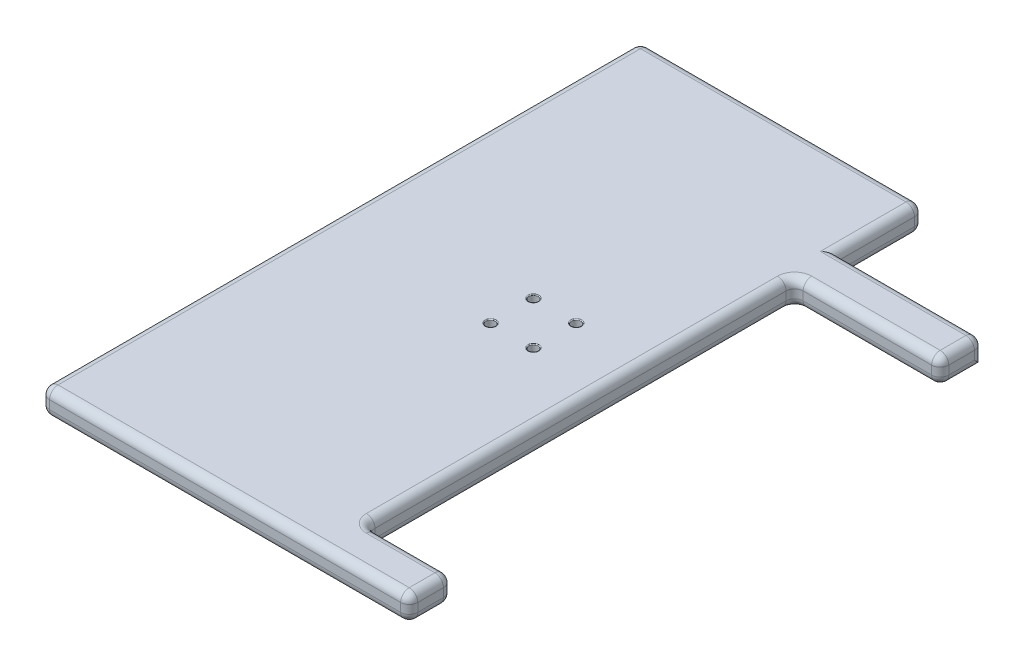
SolidWorks part; units mm, degrees
ref_plane "前视基准面" through (0, 0, 0) normal (0, 0, 1) x (1, 0, 0)
ref_plane "上视基准面" through (0, 0, 0) normal (0, 1, 0) x (1, 0, 0)
ref_plane "右视基准面" through (0, 0, 0) normal (1, 0, 0) x (0, 0, -1)
other "Configuration Table"
sketch "草图1" plane through (0, 0, 0) normal (0, 1, 0) x (1, 0, 0)
  line L0 (26, -60) -> (26, -70)
  line L1 (-60, 70) -> (6, 70)
  line L2 (-60, 70) -> (-60, -70)
  line L3 (-60, -70) -> (26, -70)
  line L4 (40, 50) -> (40, 40)
  line L5 (-55, 0) -> (55, 0) construction
  line L6 (0, -55) -> (0, 55) construction
  line L7 (6, 70) -> (6, 50)
  line L8 (6, 50) -> (40, 50)
  line L10 (40, 40) -> (6, 40)
  line L11 (6, 40) -> (6, -60)
  line L12 (6, -60) -> (26, -60)
  dimension "D1" = 6
  dimension "D2" = 6
  dimension "D3" = 70
  dimension "D4" = 140
  dimension "D5" = 40
  dimension "D6" = 20
  dimension "D7" = 10
  dimension "D8" = 60
  dimension "D9" = 10
  dimension "D10" = 20
extrude "凸台-拉伸1" add sketch "草图1" along normal blind 6
sketch "草图6" plane through (0, 0, 0) normal (0, -1, 0) x (-1, 0, 0)
  line L0 (-55, 0) -> (55, 0) construction
  line L1 (60, 70) -> (60, -70) construction
  point P0 (15, 0)
  dimension "D1" = 45
ref_axis "基准轴1" through (-15, 0, 0) along (0, -1, 0)
sketch "草图7" plane through (0, 0, 0) normal (0, -1, 0) x (1, 0, 0)
  point P0 (-20, 5)
  point P1 (-20, -5)
  point P3 (-10, 5)
  point P4 (-10, -5)
  dimension "D1" = 5
  dimension "D2" = 5
  dimension "D3" = 10
  dimension "D4" = 5
  dimension "D5" = 5
  dimension "D6" = 5
  dimension "D7" = 5
  dimension "D8" = 5
hole_wizard "M2 六角头机械螺钉的柱形沉头孔1" positions "草图8" profile "草图9" counterbore size "M2" standard "ANSI Metric" end condition up to next
sketch "草图8" plane through (0, 0, 0) normal (0, -1, 0) x (-1, 0, 0)
  point P0 (10, 5)
  point P3 (20, 5)
  point P6 (20, -5)
  point P9 (10, -5)
sketch "草图9" plane through (-10, 0, -5) normal (1, 0, 0) x (0, 0, -1)
  line L0 (0, 0) -> (0, 6)
  line L1 (0, 6) -> (1.1, 6)
  line L3 (1.1, 6) -> (1.1, 3)
  line L4 (1.1, 3) -> (2.3, 3)
  line L5 (2.3, 3) -> (2.3, 0)
  line L7 (2.3, 0) -> (0, 0)
  line L11 (0, -6.35) -> (0, 107.95) construction
  dimension "通孔孔直径" = 2.2
  dimension "通孔孔深度" = 6
  dimension "柱形沉头孔直径" = 4.6
  dimension "柱形沉头孔深度" = 3
fillet "Fillet1" radius 2 28 edges at (-17, 6, 70) (-17, 0, 70) (-60, 6, 0) (-60, 0, 0) (-60, 3, 70) (23, 0, -40) (23, 6, -40) (40, 3, -50) (40, 6, -45) (40, 0, -45) (40, 3, -40) (6, 3, -70) (6, 0, -60) (6, 6, -60) (23, 6, -50) (16, 0, 60) (16, 6, 60) (6, 3, 60) (6, 6, 10) (-27, 0, -70) (6, 0, 10) (6, 3, -40) (-27, 6, -70) (-60, 3, -70) (26, 3, 70) (26, 3, 60) (26, 0, 65) (26, 6, 65)
fillet "Fillet2" radius 0.3 4 edges at (-20, 0, -7.3) (-10, 0, -7.3) (-10, 0, 2.7) (-20, 0, 2.7)
fillet "Fillet3" radius 0.2 4 edges at (-20, 6, 6.1) (-10, 6, 6.1) (-10, 6, -3.9) (-20, 6, -3.9)
